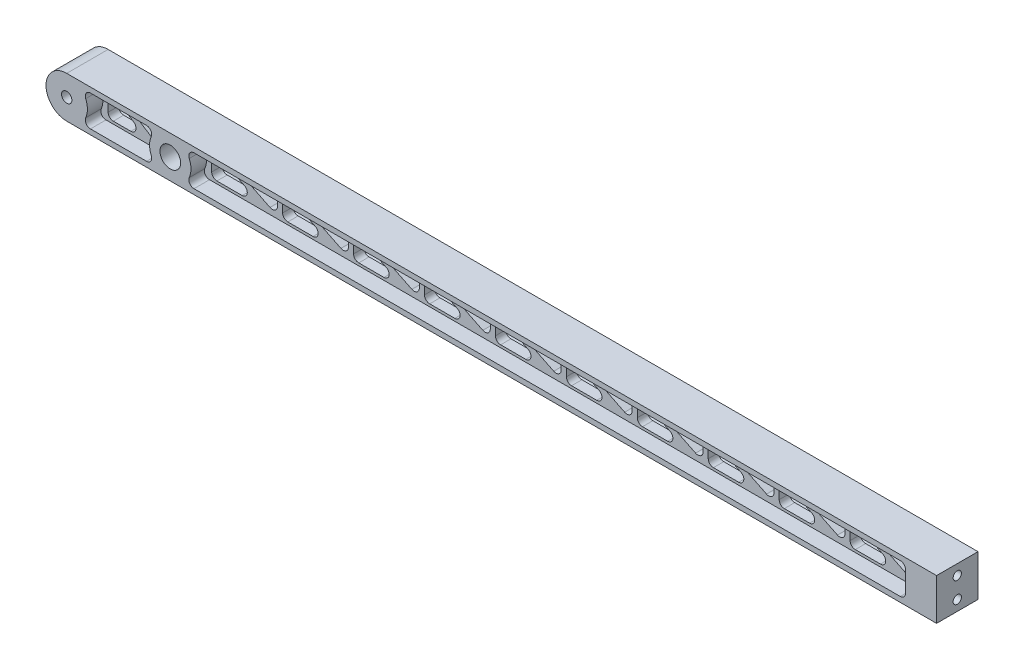
SolidWorks part; units mm, degrees
note: The reader was unsure of these and kept them because the rebuilt part matched: shared geometry of "Sketch1<10>", "Sketch3<5>".
ref_plane "Front Plane" through (0, 0, 0) normal (0, 0, 1) x (1, 0, 0)
ref_plane "Top Plane" through (0, 0, 0) normal (0, 1, 0) x (1, 0, 0)
ref_plane "Right Plane" through (0, 0, 0) normal (1, 0, 0) x (0, 0, -1)
sketch "Sketch1" plane through (0, 0, 0) normal (0, 0, 1) x (1, 0, 0)
  line L3 (609.6, 25.4) -> (609.6, 0)
  line L20 (76.2, 25.4) -> (139.7, 25.4)
  line L73 (77.3206, 12.7) -> (79.375, 12.7) construction
  line L82 (77.3206, 12.7) -> (79.375, 12.7) construction
  line L201 (76.2, 25.4) -> (609.6, 25.4)
  line L204 (77.3206, 12.7) -> (79.375, 12.7) construction
  line L205 (77.3206, 12.7) -> (79.375, 12.7) construction
  line L206 (77.3206, 12.7) -> (79.375, 12.7) construction
  line L210 (76.2, 0) -> (609.6, 0)
  circle A0 centre (76.2, 12.7) radius 3.175
  circle A1 centre (139.7, 12.7) radius 12.7
  circle A2 centre (139.7, 12.7) radius 6.35
  circle A3 centre (76.2, 12.7) radius 12.7
  dimension "D5" = 25.4
  dimension "D6" = 25.4
  dimension "D7" = 6.35
  dimension "D8" = 12.7
  dimension "D2" = 533.4
  dimension "D3" = 25.4
  dimension "D17" = 63.5
extrude "Boss-Extrude1" add sketch "Sketch1" along normal mid plane 25.4
extrude "Cut-Extrude3" cut sketch "Sketch1<10>" against normal mid plane 25.4 contours A0 | A2
sketch "Sketch1<10>" plane through (0, 0, 0) normal (0, 0, 1) x (1, 0, 0) same geometry as "Sketch1"
sketch "Sketch3" plane through (0, 0, 12.7) normal (0, 0, 1) x (1, 0, 0)
  line L0 (76.2, 25.4) -> (609.6, 25.4) construction
  line L1 (88.9, 3.175) -> (127, 3.175)
  line L2 (88.9, 3.175) -> (88.9, 22.225)
  line L3 (88.9, 22.225) -> (127, 22.225)
  line L4 (127, 3.175) -> (127, 22.225)
  line L5 (152.4, 3.175) -> (590.55, 3.175)
  line L6 (152.4, 3.175) -> (152.4, 22.225)
  line L7 (152.4, 22.225) -> (590.55, 22.225)
  line L8 (590.55, 3.175) -> (590.55, 22.225)
  line L9 (76.2, 0) -> (609.6, 0) construction
  line L10 (609.6, 25.4) -> (609.6, 0) construction
  line L11 (92.075, 20.6375) -> (92.075, 4.7625)
  line L12 (92.075, 4.7625) -> (116.8371, 4.7625)
  line L13 (116.8371, 4.7625) -> (92.075, 20.6375)
  line L14 (99.0629, 20.6375) -> (123.825, 4.7625)
  line L15 (123.825, 4.7625) -> (123.825, 20.6375)
  line L16 (123.825, 20.6375) -> (99.0629, 20.6375)
  line L17 (104.456, 12.7) -> (106.4915, 15.875)
  line L18 (155.575, 20.6375) -> (155.575, 4.7625)
  line L19 (155.575, 4.7625) -> (187.8768, 4.7625)
  line L20 (187.8768, 4.7625) -> (155.575, 20.6375)
  line L21 (163.5957, 20.6375) -> (195.8975, 4.7625)
  line L22 (195.8975, 4.7625) -> (195.8975, 20.6375)
  line L23 (195.8975, 20.6375) -> (163.5957, 20.6375)
  line L24 (173.2863, 15.875) -> (171.7259, 12.7)
  line L25 (199.0725, 20.6375) -> (199.0725, 4.7625)
  line L26 (199.0725, 4.7625) -> (231.3743, 4.7625)
  line L27 (231.3743, 4.7625) -> (199.0725, 20.6375)
  line L28 (207.0932, 20.6375) -> (239.395, 4.7625)
  line L29 (239.395, 4.7625) -> (239.395, 20.6375)
  line L30 (239.395, 20.6375) -> (207.0932, 20.6375)
  line L31 (216.7838, 15.875) -> (215.2234, 12.7)
  line L32 (242.57, 20.6375) -> (242.57, 4.7625)
  line L33 (242.57, 4.7625) -> (274.8718, 4.7625)
  line L34 (274.8718, 4.7625) -> (242.57, 20.6375)
  line L35 (250.5907, 20.6375) -> (282.8925, 4.7625)
  line L36 (282.8925, 4.7625) -> (282.8925, 20.6375)
  line L37 (282.8925, 20.6375) -> (250.5907, 20.6375)
  line L38 (260.2813, 15.875) -> (258.7209, 12.7)
  line L39 (286.0675, 20.6375) -> (286.0675, 4.7625)
  line L40 (286.0675, 4.7625) -> (318.3693, 4.7625)
  line L41 (318.3693, 4.7625) -> (286.0675, 20.6375)
  line L42 (294.0882, 20.6375) -> (326.39, 4.7625)
  line L43 (326.39, 4.7625) -> (326.39, 20.6375)
  line L44 (326.39, 20.6375) -> (294.0882, 20.6375)
  line L45 (303.7788, 15.875) -> (302.2184, 12.7)
  line L46 (329.565, 20.6375) -> (329.565, 4.7625)
  line L47 (329.565, 4.7625) -> (361.8668, 4.7625)
  line L48 (361.8668, 4.7625) -> (329.565, 20.6375)
  line L49 (337.5857, 20.6375) -> (369.8875, 4.7625)
  line L50 (369.8875, 4.7625) -> (369.8875, 20.6375)
  line L51 (369.8875, 20.6375) -> (337.5857, 20.6375)
  line L52 (347.2763, 15.875) -> (345.7159, 12.7)
  line L53 (373.0625, 20.6375) -> (373.0625, 4.7625)
  line L54 (373.0625, 4.7625) -> (405.3643, 4.7625)
  line L55 (405.3643, 4.7625) -> (373.0625, 20.6375)
  line L56 (381.0832, 20.6375) -> (413.385, 4.7625)
  line L57 (413.385, 4.7625) -> (413.385, 20.6375)
  line L58 (413.385, 20.6375) -> (381.0832, 20.6375)
  line L59 (390.7738, 15.875) -> (389.2134, 12.7)
  line L60 (416.56, 20.6375) -> (416.56, 4.7625)
  line L61 (416.56, 4.7625) -> (448.8618, 4.7625)
  line L62 (448.8618, 4.7625) -> (416.56, 20.6375)
  line L63 (424.5807, 20.6375) -> (456.8825, 4.7625)
  line L64 (456.8825, 4.7625) -> (456.8825, 20.6375)
  line L65 (456.8825, 20.6375) -> (424.5807, 20.6375)
  line L66 (434.2713, 15.875) -> (432.7109, 12.7)
  line L67 (460.0575, 20.6375) -> (460.0575, 4.7625)
  line L68 (460.0575, 4.7625) -> (492.3593, 4.7625)
  line L69 (492.3593, 4.7625) -> (460.0575, 20.6375)
  line L70 (468.0782, 20.6375) -> (500.38, 4.7625)
  line L71 (500.38, 4.7625) -> (500.38, 20.6375)
  line L72 (500.38, 20.6375) -> (468.0782, 20.6375)
  line L73 (477.7688, 15.875) -> (476.2084, 12.7)
  line L74 (503.555, 20.6375) -> (503.555, 4.7625)
  line L75 (503.555, 4.7625) -> (535.8568, 4.7625)
  line L76 (535.8568, 4.7625) -> (503.555, 20.6375)
  line L77 (511.5757, 20.6375) -> (543.8775, 4.7625)
  line L78 (543.8775, 4.7625) -> (543.8775, 20.6375)
  line L79 (543.8775, 20.6375) -> (511.5757, 20.6375)
  line L80 (521.2663, 15.875) -> (519.7059, 12.7)
  line L81 (547.0525, 20.6375) -> (547.0525, 4.7625)
  line L82 (547.0525, 4.7625) -> (579.3543, 4.7625)
  line L83 (579.3543, 4.7625) -> (547.0525, 20.6375)
  line L84 (555.0732, 20.6375) -> (587.375, 4.7625)
  line L85 (587.375, 4.7625) -> (587.375, 20.6375)
  line L86 (587.375, 20.6375) -> (555.0732, 20.6375)
  line L87 (564.7638, 15.875) -> (563.2034, 12.7)
  line L88 (127, 22.225) -> (152.4, 22.225)
  line L89 (127, 3.175) -> (152.4, 3.175)
  line L90 (88.9, 22.225) -> (76.2, 22.225)
  line L91 (76.2, 22.225) -> (76.2, 3.175)
  line L92 (76.2, 3.175) -> (88.9, 3.175)
  circle A0 centre (76.2, 12.7) radius 12.7
  circle A1 centre (139.7, 12.7) radius 12.7
  point P18 (609.6, 12.7)
  dimension "D3" = 25.4
  dimension "D4" = 25.4
  dimension "D1" = 3.175
  dimension "D2" = 3.175
  dimension "D5" = 19.05
  dimension "D6" = 3.175
  dimension "D7" = 3.175
  dimension "D8" = 1.5875
  dimension "D9" = 1.5875
  dimension "D10" = 3.175
  dimension "D11" = 3.175
  dimension "D12" = 3.175
  dimension "D13" = 1.5875
  dimension "D14" = 1.5875
  dimension "D15" = 3.175
  dimension "D16" = 3.175
  dimension "D18" = 1.5875
  dimension "D19" = 10
  dimension "D20" = 3.175
  dimension "D17" = 1.5875
  dimension "D21" = 3.175
extrude "Cut-Extrude5" cut sketch "Sketch3" against normal through all contours L12 L13 L11 | L15 L16 L14 | L19 L20 L18 | L22 L23 L21 | L26 L27 L25 | L29 L30 L28 | L40 L41 L39 | L47 L48 L46 | L50 L51 L49 | L54 L55 L53 | L57 L58 L56 | L61 L62 L60 | L64 L65 L63 | L68 L69 L67 | L71 L72 L70 | L75 L76 L74 | L78 L79 L77 | L82 L83 L81 | L85 L86 L84 | L34 L32 L33 | L37 L35 L36 | L44 L42 L43
extrude "Cut-Extrude7" cut sketch "Sketch3<5>" against normal blind 9.525
sketch "Sketch3<5>" plane through (0, 0, 12.7) normal (0, 0, 1) x (1, 0, 0) same geometry as "Sketch3"
mirror "Mirror1" about plane through (0, 0, 0) normal (0, 0, 1) of "Cut-Extrude7"
fillet "Fillet1" radius 3.175 82 edges at (148.1003, 3.175, 7.9375) (148.1003, 22.225, 7.9375) (590.55, 22.225, 7.9375) (590.55, 3.175, 7.9375) (131.2997, 3.175, 7.9375) (84.6003, 3.175, 7.9375) (84.6003, 22.225, 7.9375) (131.2997, 22.225, 7.9375) (294.0882, 20.6375, 0) (326.39, 20.6375, 0) (326.39, 4.7625, 0) (250.5907, 20.6375, 0) (282.8925, 20.6375, 0) (282.8925, 4.7625, 0) (242.57, 20.6375, 0) (274.8718, 4.7625, 0) (242.57, 4.7625, 0) (555.0732, 20.6375, 0) (587.375, 20.6375, 0) (587.375, 4.7625, 0) (547.0525, 20.6375, 0) (579.3543, 4.7625, 0) (547.0525, 4.7625, 0) (511.5757, 20.6375, 0) (543.8775, 20.6375, 0) (543.8775, 4.7625, 0) (503.555, 20.6375, 0) (535.8568, 4.7625, 0) (503.555, 4.7625, 0) (468.0782, 20.6375, 0) (500.38, 20.6375, 0) (500.38, 4.7625, 0) (460.0575, 20.6375, 0) (492.3593, 4.7625, 0) (460.0575, 4.7625, 0) (424.5807, 20.6375, 0) (456.8825, 20.6375, 0) (456.8825, 4.7625, 0) (416.56, 20.6375, 0) (448.8618, 4.7625, 0) (416.56, 4.7625, 0) (381.0832, 20.6375, 0) (413.385, 20.6375, 0) (413.385, 4.7625, 0) (373.0625, 20.6375, 0) (405.3643, 4.7625, 0) (373.0625, 4.7625, 0) (337.5857, 20.6375, 0) (369.8875, 20.6375, 0) (369.8875, 4.7625, 0) (329.565, 20.6375, 0) (361.8668, 4.7625, 0) (329.565, 4.7625, 0) (286.0675, 20.6375, 0) (318.3693, 4.7625, 0) (286.0675, 4.7625, 0) (207.0932, 20.6375, 0) (239.395, 20.6375, 0) (239.395, 4.7625, 0) (199.0725, 20.6375, 0) (231.3743, 4.7625, 0) (199.0725, 4.7625, 0) (163.5957, 20.6375, 0) (195.8975, 20.6375, 0) (195.8975, 4.7625, 0) (155.575, 20.6375, 0) (187.8768, 4.7625, 0) (155.575, 4.7625, 0) (148.1003, 22.225, -7.9375) (148.1003, 3.175, -7.9375) (590.55, 3.175, -7.9375) (590.55, 22.225, -7.9375) (99.0629, 20.6375, 0) (123.825, 20.6375, 0) (123.825, 4.7625, 0) (92.075, 20.6375, 0) (116.8371, 4.7625, 0) (92.075, 4.7625, 0) (84.6003, 3.175, -7.9375) (131.2997, 3.175, -7.9375) (131.2997, 22.225, -7.9375) (84.6003, 22.225, -7.9375)
sketch "Sketch2" plane through (609.6, 0, 0) normal (1, 0, 0) x (0, 0, -1)
  line L0 (0, 25.4) -> (0, 0) construction
  line L1 (-12.7, 25.4) -> (12.7, 25.4) construction
  line L2 (-12.7, 0) -> (12.7, 0) construction
  line L3 (-12.7, 12.7) -> (12.7, 12.7) construction
  line L4 (-12.7, 25.4) -> (-12.7, 0) construction
  line L5 (12.7, 25.4) -> (12.7, 0) construction
  line L6 (0, 25.4) -> (0, 19.05) construction
  line L7 (0, 0) -> (0, 6.35) construction
  circle A0 centre (0, 19.05) radius 6.35
  circle A1 centre (0, 6.35) radius 6.35
  dimension "D3" = 12.7
  dimension "D4" = 12.7
  dimension "D1" = 6.35
  dimension "D2" = 6.35
hole_wizard "1/4-20 Tapped Hole1" positions "3DSketch1" profile "Sketch4" tap size "1/4-20" standard "ANSI Inch"
sketch3d "3DSketch1"
  point P0 (609.6, 19.05, 0)
  point P3 (609.6, 6.35, 0)
sketch "Sketch4" plane through (609.6, 19.05, 0) normal (0, 1, 0) x (0, 0, -1)
  line L0 (0, 0) -> (0, 14.2338)
  line L1 (0, 14.2338) -> (2.5527, 12.7)
  line L2 (2.5527, 12.7) -> (2.5527, 0)
  line L5 (2.5527, 0) -> (0, 0)
  line L10 (0, 14.2338) -> (-2.5527, 12.7) construction
  line L11 (0, -6.35) -> (0, 107.95) construction
  dimension "Tap Drill Dia." = 5.1054
  dimension "Tap Drill Depth" = 12.7
  dimension "Drill Angle" = 118
cosmetic thread "Hole Thread1" parameters "D1"=12.7, "D2"=6.35
cosmetic thread "Hole Thread2" parameters "D1"=12.7, "D2"=6.35
